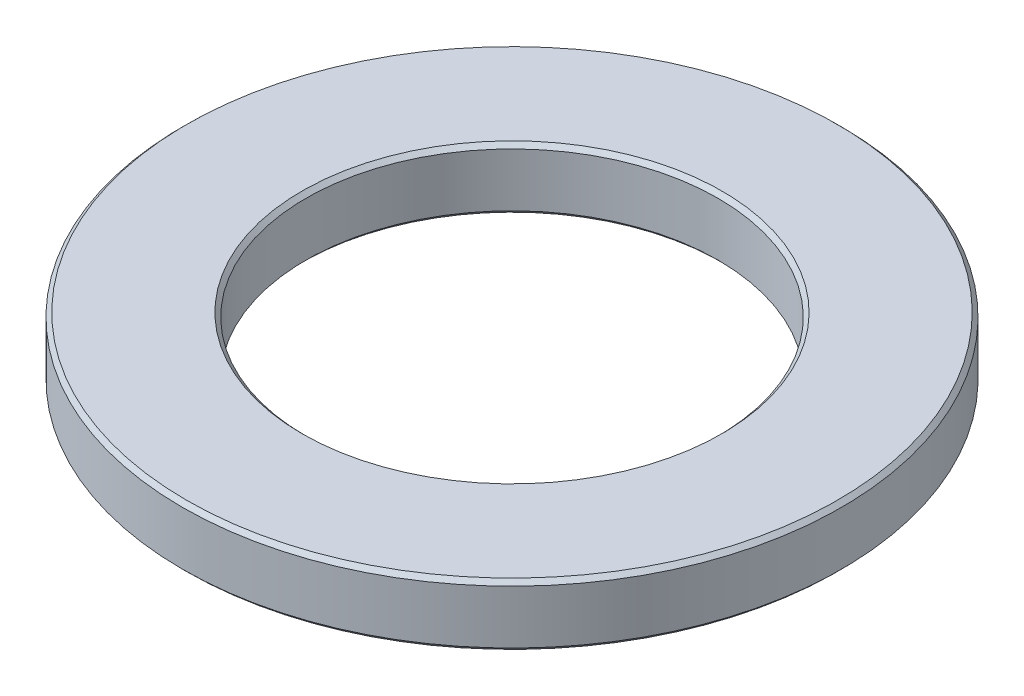
SolidWorks part; units mm, degrees
material "6061-T6 (SS)"
ref_plane "Front Plane" through (0, 0, 0) normal (0, 0, 1) x (1, 0, 0)
ref_plane "Top Plane" through (0, 0, 0) normal (0, 1, 0) x (1, 0, 0)
ref_plane "Right Plane" through (0, 0, 0) normal (1, 0, 0) x (0, 0, -1)
sketch "ProfileS" plane through (0, 0, 0) normal (0, 1, 0) x (1, 0, 0)
  circle A0 centre (0, 0) radius 5
  circle A1 centre (0, 0) radius 8
  dimension "InnerDia" = 10
  dimension "RefDia" = 16
  dimension "DiaControl" = 3
extrude "Profile" add sketch "ProfileS" along normal blind 1.5
chamfer "OuterC" distance 0.1 angle 45 2 edges at (0, 0, 8) (0, 1.5, 8)
chamfer "InnerC" distance 0.1 angle 45 2 edges at (0, 0, 5) (0, 1.5, 5)
